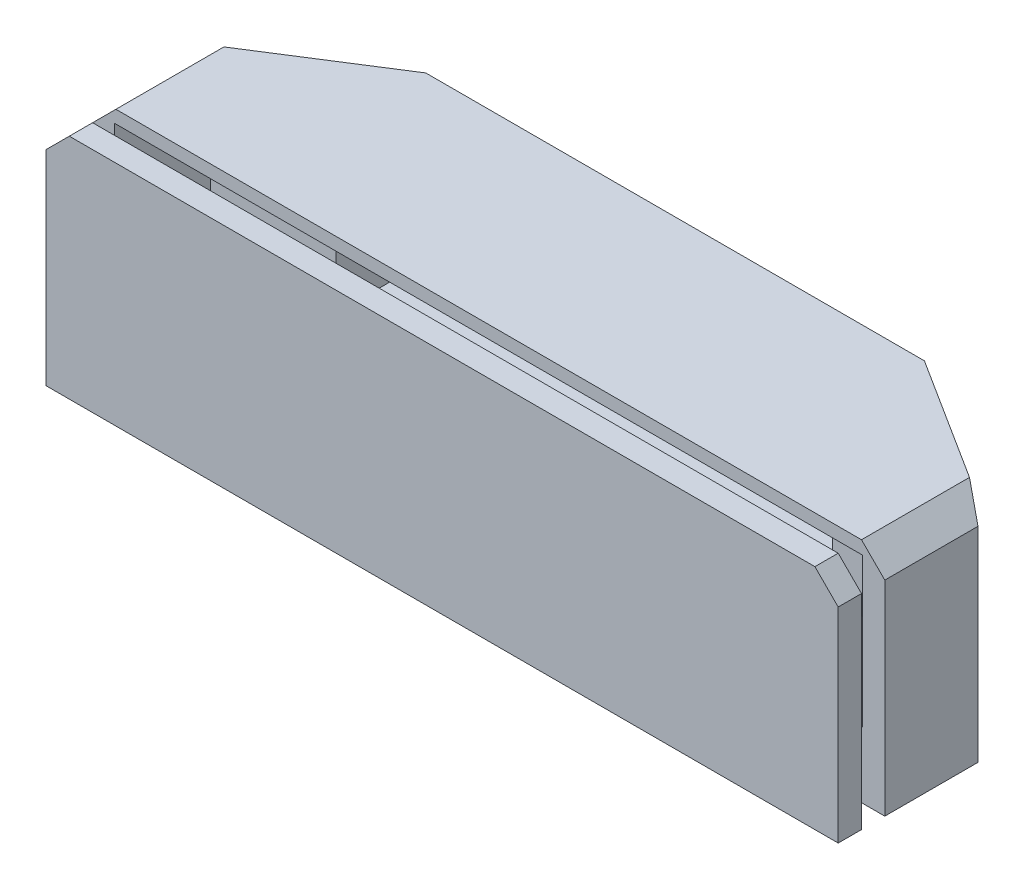
SolidWorks part; units mm, degrees
ref_plane "Front Plane" through (0, 0, 0) normal (0, 0, 1) x (1, 0, 0)
ref_plane "Top Plane" through (0, 0, 0) normal (0, 1, 0) x (1, 0, 0)
ref_plane "Right Plane" through (0, 0, 0) normal (1, 0, 0) x (0, 0, -1)
sketch "Sketch1" plane through (0, 0, 0) normal (0, 0, 1) x (1, 0, 0)
  line L1 (-21.3, 6.4) -> (21.3, 6.4)
  line L2 (-21.3, 6.4) -> (-21.3, -6.4)
  line L3 (-21.3, -6.4) -> (21.3, -6.4)
  line L4 (21.3, 6.4) -> (21.3, -6.4)
  line L5 (-21.3, 6.4) -> (21.3, -6.4) construction
  line L6 (-21.3, -6.4) -> (21.3, 6.4) construction
  point P0 (0, 0)
  dimension "D1" = 42.6
  dimension "D2" = 12.8
sketch "Sketch2" plane through (0, 0, 0) normal (0, 1, 0) x (1, 0, 0)
  line L5 (-34, 0.0554) -> (-21.4, 8.0554)
  line L6 (-21.4, 8.0554) -> (21.4, 8.0554)
  line L8 (0, -1.5931) -> (0, 13.1633) construction
  line L9 (21.4, 8.0554) -> (34, 0.0554)
  line L10 (34, 0.0554) -> (34, -7.9446)
  line L11 (34, -7.9446) -> (-34, -7.9446)
  line L12 (-34, -7.9446) -> (-34, 0.0554)
  point P2 (-34, -5.06)
  point P8 (-34, -6.2313)
  point P9 (-34, 0)
  dimension "D1" = 16
  dimension "D2" = 68
  dimension "D3" = 42.8
  dimension "D4" = 8
extrude "Boss-Extrude1" add sketch "Sketch2" along normal blind 7.5 and the other way blind 12.05
extrude "Cut-Extrude1" cut sketch "Sketch1" against normal blind 7.2
extrude "Cut-Extrude2" cut sketch "Sketch1<2>" along normal through all
sketch "Sketch1<2>" plane through (0, 0, 0) normal (0, 0, 1) x (1, 0, 0) same geometry as "Sketch1"
sketch "Sketch3" plane through (0, 0, 7.9446) normal (0, 0, 1) x (1, 0, 0)
  line L1 (-32.1, 6.4) -> (32.1, 6.4)
  line L2 (-32.1, 6.4) -> (-32.1, -6.4)
  line L3 (-32.1, -6.4) -> (32.1, -6.4)
  line L4 (32.1, 6.4) -> (32.1, -6.4)
  line L5 (-32.1, 6.4) -> (32.1, -6.4) construction
  line L6 (-32.1, -6.4) -> (32.1, 6.4) construction
  point P0 (0, 0)
  dimension "D1" = 12.8
  dimension "D2" = 64.2
extrude "Cut-Extrude3" cut sketch "Sketch3" against normal blind 8.2
sketch "Sketch4" plane through (0, 0, 7.9446) normal (0, 0, 1) x (1, 0, 0)
  line L4 (34, -12.05) -> (34, 7.5)
  line L5 (34, 7.5) -> (-34, 7.5)
  line L6 (-34, 7.5) -> (-34, -12.05)
  line L7 (-34, -12.05) -> (34, -12.05)
  line L8 (34, -12.05) -> (34, 7.5)
  line L9 (34, 7.5) -> (-34, 7.5)
  line L10 (-34, 7.5) -> (-34, -12.05)
  line L11 (-34, -12.05) -> (34, -12.05)
  dimension "D1" = 0
extrude "Boss-Extrude2" add sketch "Sketch4" along normal blind 2 from offset 2 separate body
chamfer "Chamfer1" distance 2 angle 45 2 edges at (34, 7.5, 3.9446) (-34, 7.5, 3.9446)
chamfer "Chamfer2" distance 2 angle 45 2 edges at (34, 7.5, 10.9446) (-34, 7.5, 10.9446)
